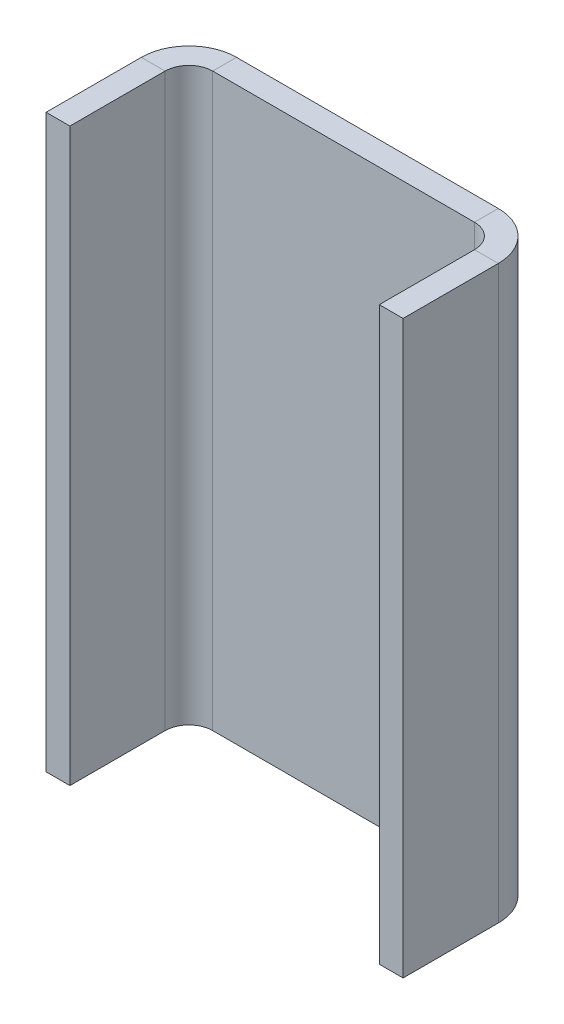
SolidWorks part; units mm, degrees
note: The reader was unsure of these and kept them because the rebuilt part matched: flange length of "Edge-Flange1", "Edge-Flange2".
material "1.0553 (S355J0)"
ref_plane "Front Plane" through (0, 0, 0) normal (0, 0, 1) x (1, 0, 0)
ref_plane "Top Plane" through (0, 0, 0) normal (0, 1, 0) x (1, 0, 0)
ref_plane "Right Plane" through (0, 0, 0) normal (1, 0, 0) x (0, 0, -1)
sketch "Sketch1" plane through (0, 0, 0) normal (0, 0, 1) x (1, 0, 0)
  line L1 (-32.5, 0) -> (32.5, 0)
  line L2 (-32.5, 0) -> (-32.5, -120)
  line L3 (-32.5, -120) -> (32.5, -120)
  line L4 (32.5, 0) -> (32.5, -120)
  dimension "D1" = 65
  dimension "D2" = 120
base flange "Base-Flange1" sketch "Sketch1" thickness 5 reverse thickness direction no parameters "D1"=5
edge flange "Edge-Flange1" sketch "Sketch8" flange angle 90 flange length 30 flange position material outside bend radius 5 thickness 5 relief rectangular parameters "D1"=10, "D6"=10
sketch "Sketch8" plane through (32.5, 0, 0) normal (-1, 0, 0) x (0, -1, 0)
  line L2 (0, 0) -> (0, 25)
  line L3 (0, 25) -> (120, 25)
  line L4 (120, 25) -> (120, 0)
  line L6 (120, 0) -> (0, 0) construction
  line L7 (120, 0) -> (0, 0)
bend "EdgeBend1" bend radius 5 bend angle 90 parameters "D5"=1
edge flange "Edge-Flange2" sketch "Sketch11" flange angle 90 flange length 30 flange position material outside bend radius 5 thickness 5 relief rectangular parameters "D6"=10
sketch "Sketch11" plane through (-32.5, 0, 0) normal (1, 0, 0) x (0, 1, 0)
  line L2 (-120, 0) -> (-120, 25)
  line L3 (-120, 25) -> (0, 25)
  line L4 (0, 25) -> (0, 0)
  line L6 (0, 0) -> (-120, 0) construction
  line L7 (0, 0) -> (-120, 0)
bend "EdgeBend2" bend radius 5 bend angle 90 parameters "D5"=2
sketch "Bend-Lines1" [suppressed] plane through (0, 0, 0) normal (0, 1, 0) x (1, 0, 0)
sketch "Bounding-Box1" [suppressed] plane through (0, 0, 0) normal (0, 1, 0) x (1, 0, 0)
sheet metal parameters "Sheet-Metal1" thickness 5 parameters "D1"=10
flat pattern "Flat-Pattern1" [suppressed]
sketch "Bend-Lines2" plane through (0, 0, 0) normal (0, 1, 0) x (1, 0, 0)
sketch3d "Bounding-Box2" [suppressed]
  line L0 (37.5, 0, 0) -> (37.5, -120, 0) construction
  line L1 (-37.5, 0, 0) -> (-37.5, -120, 0) construction
  line L2 (37.5, 0, 0) -> (-37.5, 0, 0) construction
  line L3 (37.5, -120, 0) -> (-37.5, -120, 0) construction
sheet metal parameters "Sheet-Metal2" thickness 5 parameters "D1"=10
flat pattern "Flat-Pattern1"
sketch "Bend-Lines2" plane through (0, 0, 0) normal (0, 0, 1) x (1, 0, 0)
  line L0 (38.1941, -120) -> (38.1941, 0) construction
  line L1 (38.1941, -120) -> (38.1941, 0) construction
sketch3d "Bounding-Box2" [suppressed]
  line L0 (63.8883, 0, 0) -> (63.8883, -120, 0) construction
  line L1 (-37.5, 0, 0) -> (-37.5, -120, 0) construction
  line L2 (63.8883, 0, 0) -> (-37.5, 0, 0) construction
  line L3 (63.8883, -120, 0) -> (-37.5, -120, 0) construction
bend of the flat pattern "Flatten-<EdgeBend1>1"
sheet metal parameters "Sheet-Metal3" thickness 5 parameters "D1"=10
flat pattern "Flat-Pattern1"
sketch "Bend-Lines2" plane through (0, 0, 0) normal (0, 0, 1) x (1, 0, 0)
  line L0 (33.1941, -120) -> (33.1941, 0) construction
  line L1 (33.1941, -120) -> (33.1941, 0) construction
  line L2 (-33.1941, 0) -> (-33.1941, -120) construction
  line L3 (-33.1941, 0) -> (-33.1941, -120) construction
sketch3d "Bounding-Box2" [suppressed]
  line L0 (58.8883, 0, 0) -> (58.8883, -120, 0) construction
  line L1 (-58.8883, 0, 0) -> (-58.8883, -120, 0) construction
  line L2 (58.8883, 0, 0) -> (-58.8883, 0, 0) construction
  line L3 (58.8883, -120, 0) -> (-58.8883, -120, 0) construction
bend of the flat pattern "Flatten-<EdgeBend1>1"
bend of the flat pattern "Flatten-<EdgeBend2>1"
